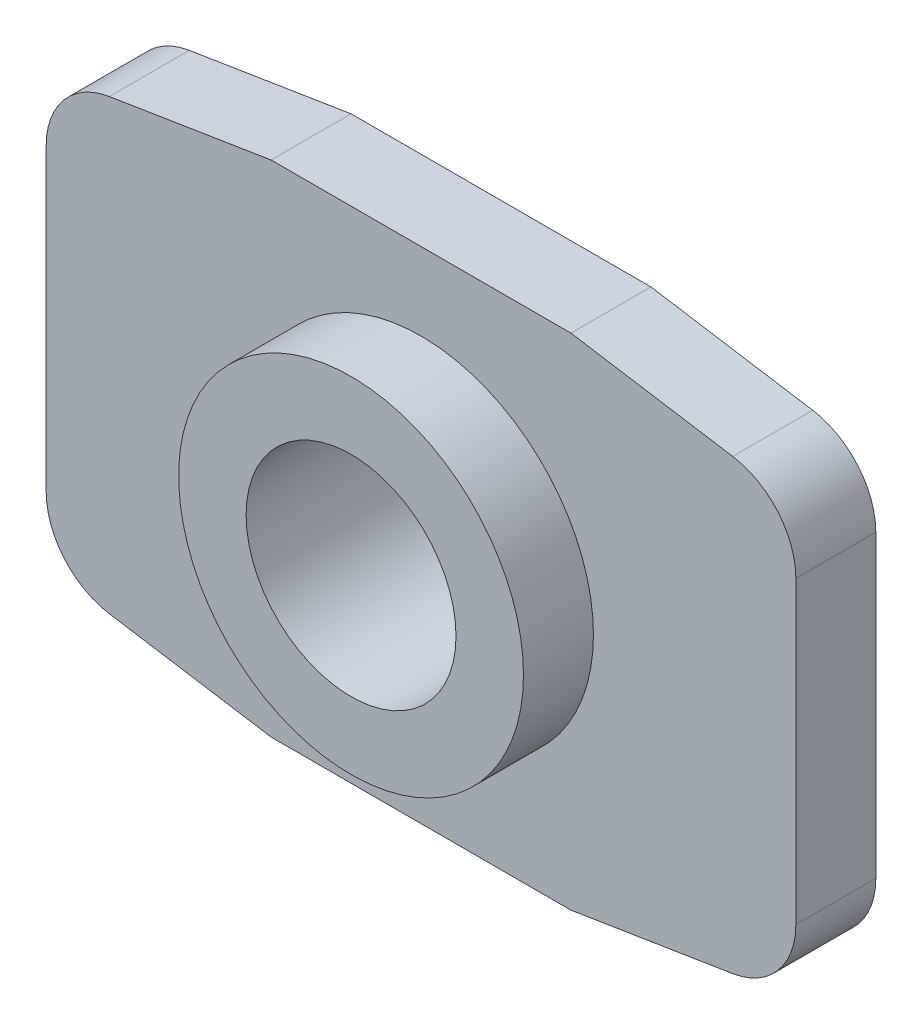
SolidWorks part; units mm, degrees
material "Plain Carbon Steel"
ref_plane "Front Plane" through (0, 0, 0) normal (0, 0, 1) x (1, 0, 0)
ref_plane "Top Plane" through (0, 0, 0) normal (0, 1, 0) x (1, 0, 0)
ref_plane "Right Plane" through (0, 0, 0) normal (1, 0, 0) x (0, 0, -1)
sketch "Sketch1" plane through (0, 0, 0) normal (0, 0, 1) x (1, 0, 0)
  line L0 (-7.5, 0) -> (7.5, 0) construction
  line L1 (-6.2374, 4.4811) -> (-3, 5)
  line L2 (-7.5, -3) -> (-7.5, 3)
  line L3 (-3, 5) -> (3, 5)
  line L4 (7.5, -3) -> (7.5, 3)
  line L5 (0, 5) -> (0, 0) construction
  line L6 (6.2374, 4.4811) -> (3, 5)
  line L7 (6.2374, -4.4811) -> (3, -5)
  line L8 (-3, -5) -> (3, -5)
  line L9 (-6.2374, -4.4811) -> (-3, -5)
  arc A0 (7.5, 3) -> (6.2374, 4.4811) centre (6, 3) ccw
  arc A1 (-7.5, -3) -> (-6.2374, -4.4811) centre (-6, -3) ccw
  arc A2 (7.5, -3) -> (6.2374, -4.4811) centre (6, -3) cw
  arc A3 (-7.5, 3) -> (-6.2374, 4.4811) centre (-6, 3) cw
  dimension "D3" = 6
  dimension "D5" = 1.5
  dimension "D1" = 15
  dimension "D2" = 10
  dimension "D4" = 6
extrude "Boss-Extrude1" add sketch "Sketch1" along normal blind 1.6
sketch "Sketch2" plane through (0, 0, 1.6) normal (0, 0, 1) x (1, 0, 0)
  line L0 (-7.5, 0) -> (0, 0) construction
  line L1 (-7.5, 3) -> (-7.5, -3) construction
  line L2 (0, 0) -> (0, 5) construction
  line L4 (3, 5) -> (-3, 5) construction
  circle A0 centre (0, 0) radius 3.45
  dimension "D2" = 6.9
extrude "Boss-Extrude2" add sketch "Sketch2" along normal blind 1.4
hole_wizard "M5x0.8 Tapped Hole1" positions "Sketch4" profile "Sketch3" tap size "M5x0.8" standard "ANSI Metric" end condition through all
sketch "Sketch4" plane through (0, 0, 3) normal (0, 0, 1) x (1, 0, 0)
  point P0 (0, 0)
sketch "Sketch3" plane through (0, 0, 3) normal (1, 0, 0) x (0, -1, 0)
  line L0 (0, 0) -> (0, 3)
  line L1 (0, 3) -> (2.1, 3)
  line L2 (2.1, 3) -> (2.1, 0)
  line L5 (2.1, 0) -> (0, 0)
  line L11 (0, -6.35) -> (0, 107.95) construction
  dimension "Thread Major Dia." = 4.2
  dimension "Thru Tap Drill Depth" = 3
